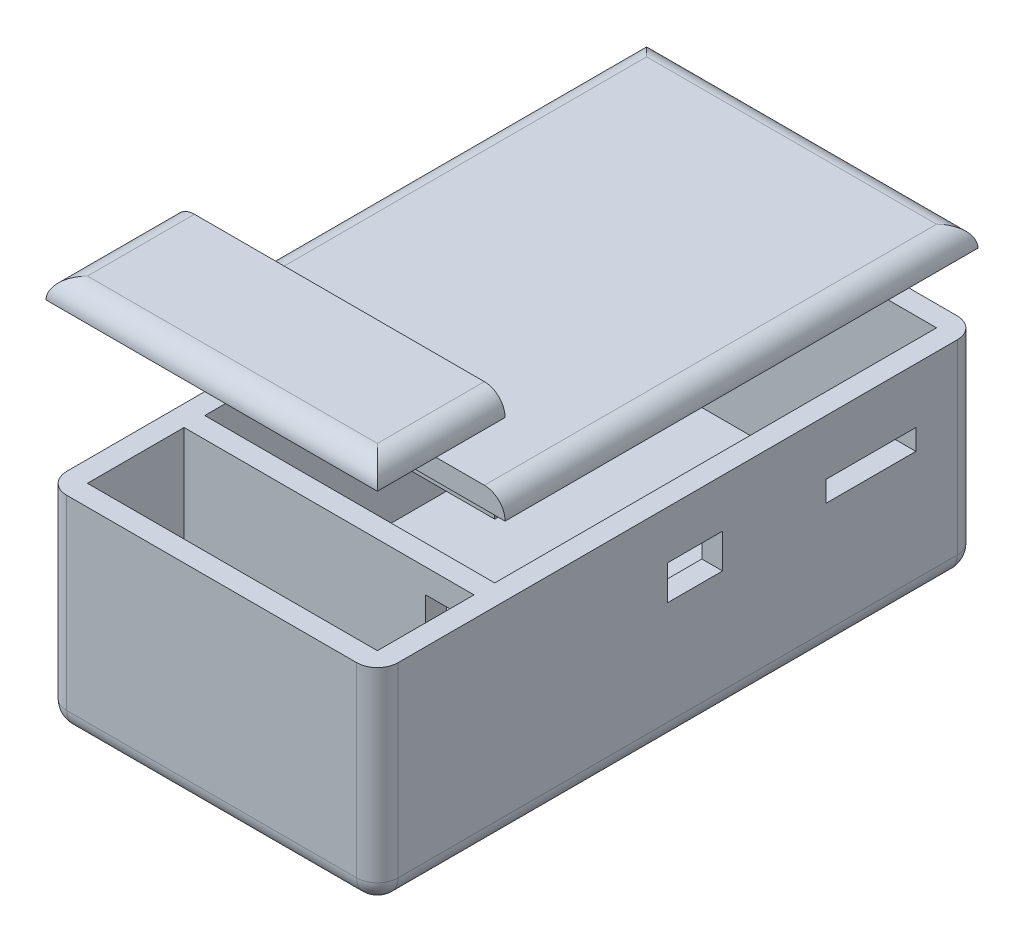
SolidWorks part; units mm, degrees
ref_plane "Front Plane" through (0, 0, 0) normal (0, 0, 1) x (1, 0, 0)
ref_plane "Top Plane" through (0, 0, 0) normal (0, 1, 0) x (1, 0, 0)
ref_plane "Right Plane" through (0, 0, 0) normal (1, 0, 0) x (0, 0, -1)
sketch "Sketch1" plane through (0, 0, 0) normal (0, 1, 0) x (1, 0, 0)
  line L0 (53.34, 40.64) -> (53.34, -12.7) construction
  line L5 (0, 0) -> (53.34, 0)
  line L6 (0, 0) -> (0, 81.28)
  line L11 (0, 81.28) -> (53.34, 81.28)
  line L12 (53.34, 0) -> (53.34, 81.28)
  line L13 (0, -3.81) -> (53.34, -3.81)
  line L14 (0, -3.81) -> (0, -21.59)
  line L15 (0, -21.59) -> (53.34, -21.59)
  line L16 (53.34, -3.81) -> (53.34, -21.59)
  line L17 (0, 40.64) -> (0, -12.7) construction
  dimension "D1" = 3.81
  dimension "D2" = 17.78
  dimension "D3" = 81.28
  dimension "D4" = 53.34
sketch "Sketch3" plane through (0, 0, 0) normal (0, 1, 0) x (1, 0, 0)
  line L0 (53.34, 0) -> (53.34, 81.28) construction
  line L1 (-3.81, -25.4) -> (57.15, -25.4)
  line L2 (-3.81, -25.4) -> (-3.81, 85.09)
  line L3 (-3.81, 85.09) -> (57.15, 85.09)
  line L4 (57.15, -25.4) -> (57.15, 85.09)
  line L5 (0, 81.28) -> (53.34, 81.28) construction
  line L6 (0, 0) -> (0, 81.28) construction
  line L7 (0, -21.59) -> (53.34, -21.59) construction
  dimension "D1" = 3.81
  dimension "D2" = 3.81
  dimension "D3" = 3.81
  dimension "D4" = 3.81
extrude "Boss-Extrude2" add sketch "Sketch3" against normal blind 38.1
extrude "Cut-Extrude1" cut sketch "Sketch1" against normal blind 34.29
sketch "Sketch4" plane through (0, 0, 3.81) normal (0, 0, 1) x (1, 0, 0)
  line L0 (57.15, -38.1) -> (57.15, 0) construction
  line L1 (44.45, -4.445) -> (53.34, -4.445)
  line L2 (44.45, -4.445) -> (44.45, -29.845)
  line L3 (44.45, -29.845) -> (53.34, -29.845)
  line L4 (53.34, -4.445) -> (53.34, -29.845)
  line L5 (57.15, -34.29) -> (-3.81, -34.29) construction
  line L6 (-3.81, -38.1) -> (-3.81, 0) construction
  line L7 (-3.81, -38.1) -> (57.15, -38.1) construction
  line L8 (57.15, -34.29) -> (57.15, 0) construction
  line L9 (53.34, -17.145) -> (57.15, -17.145) construction
  dimension "D1" = 8.89
  dimension "D2" = 25.4
  dimension "D3" = 3.81
  dimension "D4" = 3.81
extrude "Cut-Extrude2" cut sketch "Sketch4" against normal up to surface (3.81 mm away) up to face at (26.67, -17.145, 0)
sketch "Sketch5" plane through (53.34, 0, 0) normal (-1, 0, 0) x (0, 0, 1)
  line L1 (-38.1, -8.89) -> (-27.94, -8.89)
  line L2 (-38.1, -8.89) -> (-38.1, -15.24)
  line L3 (-38.1, -15.24) -> (-27.94, -15.24)
  line L4 (-27.94, -8.89) -> (-27.94, -15.24)
  line L5 (0, -34.29) -> (0, -29.845) construction
  line L6 (0, -34.29) -> (-81.28, -34.29) construction
  line L8 (-81.28, -34.29) -> (-81.28, 0) construction
  line L9 (-73.66, -10.16) -> (-57.15, -10.16)
  line L10 (-73.66, -10.16) -> (-73.66, -13.97)
  line L11 (-73.66, -13.97) -> (-57.15, -13.97)
  line L12 (-57.15, -10.16) -> (-57.15, -13.97)
  line L13 (-57.15, -12.065) -> (-38.1, -12.065) construction
  dimension "D1" = 10.16
  dimension "D2" = 6.35
  dimension "D3" = 38.1
  dimension "D4" = 25.4
  dimension "D5" = 16.51
  dimension "D6" = 3.81
  dimension "D7" = 7.62
extrude "Cut-Extrude3" cut sketch "Sketch5" against normal up to surface (3.81 mm away) up to face at (57.15, -19.05, -29.845)
sketch "Sketch6" plane through (0, 0, 0) normal (1, 0, 0) x (0, 0, -1)
  line L0 (81.28, -34.29) -> (81.28, 0) construction
  line L1 (56.388, -11.049) -> (68.58, -11.049)
  line L2 (56.388, -11.049) -> (56.388, -23.241)
  line L3 (56.388, -23.241) -> (68.58, -23.241)
  line L4 (68.58, -11.049) -> (68.58, -23.241)
  line L5 (68.58, -17.145) -> (81.28, -17.145) construction
  dimension "D1" = 12.192
  dimension "D2" = 12.192
  dimension "D3" = 12.7
extrude "Cut-Extrude4" cut sketch "Sketch6" against normal up to surface (3.81 mm away) up to face at (-3.81, -19.05, -29.845)
ref_plane "Plane1" through (0, 12.7, 0) normal (0, 1, 0) x (1, 0, 0)
sketch "Sketch8" plane through (0, 12.7, 0) normal (0, 1, 0) x (1, 0, 0)
  line L0 (57.15, -25.4) -> (57.15, 85.09) construction
  line L5 (-3.81, 85.09) -> (57.15, 85.09)
  line L6 (-3.81, 85.09) -> (-3.81, -1.905)
  line L7 (-3.81, -1.905) -> (57.15, -1.905)
  line L8 (57.15, 85.09) -> (57.15, -1.905)
  line L9 (0, 0) -> (53.34, 0) construction
  dimension "D1" = 1.905
extrude "Boss-Extrude3" add sketch "Sketch8" along normal blind 3.81 separate body
ref_plane "Plane2" through (0, 29.21, 0) normal (0, 1, 0) x (1, 0, 0)
sketch "Sketch9" plane through (0, 29.21, 0) normal (0, 1, 0) x (1, 0, 0)
  line L1 (-3.81, -25.4) -> (57.15, -25.4)
  line L2 (-3.81, -25.4) -> (-3.81, -1.905)
  line L3 (-3.81, -1.905) -> (57.15, -1.905)
  line L4 (57.15, -25.4) -> (57.15, -1.905)
extrude "Boss-Extrude4" add sketch "Sketch9" along normal blind 3.81
sketch "Sketch10" plane through (0, 12.7, 0) normal (0, -1, 0) x (1, 0, 0)
  line L0 (57.15, 25.4) -> (57.15, -85.09) construction
  line L1 (0, 0) -> (53.34, 0)
  line L2 (0, 0) -> (0, -81.28)
  line L3 (0, -81.28) -> (53.34, -81.28)
  line L4 (53.34, 0) -> (53.34, -81.28)
  line L5 (57.15, -85.09) -> (-3.81, -85.09) construction
  line L6 (-3.81, -85.09) -> (-3.81, 25.4) construction
  line L14 (53.34, 3.81) -> (0, 3.81) construction
  dimension "D1" = 3.81
  dimension "D2" = 3.81
  dimension "D3" = 3.81
  dimension "D8" = 3.81
extrude "Boss-Extrude5" add sketch "Sketch10" along normal blind 2.54
sketch "Sketch11" plane through (0, 29.21, 0) normal (0, -1, 0) x (1, 0, 0)
  line L0 (-3.81, 25.4) -> (57.15, 25.4) construction
  line L1 (0, 21.59) -> (53.34, 21.59)
  line L2 (0, 21.59) -> (0, 3.81)
  line L3 (0, 3.81) -> (53.34, 3.81)
  line L4 (53.34, 21.59) -> (53.34, 3.81)
  line L5 (57.15, 25.4) -> (57.15, -85.09) construction
  line L6 (-3.81, -85.09) -> (-3.81, 25.4) construction
  line L7 (0, 0) -> (53.34, 0) construction
  dimension "D1" = 3.81
  dimension "D2" = 3.81
  dimension "D3" = 3.81
  dimension "D4" = 3.81
extrude "Boss-Extrude6" add sketch "Sketch11" along normal blind 2.54
fillet "Fillet1" radius 3.81 8 edges at (-3.81, -19.05, 25.4) (57.15, -19.05, 25.4) (-3.81, -19.05, -85.09) (57.15, -19.05, -85.09) (26.67, -38.1, -85.09) (-3.81, -38.1, -29.845) (26.67, -38.1, 25.4) (57.15, -38.1, -29.845)
fillet "Fillet2" radius 3.81 3 edges at (57.15, 16.51, -41.5925) (26.67, 16.51, -85.09) (-3.81, 16.51, -41.5925)
fillet "Fillet3" radius 3.81 3 edges at (57.15, 33.02, 13.6525) (26.67, 33.02, 25.4) (-3.81, 33.02, 13.6525)
sketch "Sketch12" plane through (0, 10.16, 0) normal (0, -1, 0) x (1, 0, 0)
  line L0 (0, 0) -> (0, -81.28) construction
  line L1 (5.08, -5.08) -> (48.26, -5.08)
  line L2 (5.08, -5.08) -> (5.08, -76.2)
  line L3 (5.08, -76.2) -> (48.26, -76.2)
  line L4 (48.26, -5.08) -> (48.26, -76.2)
  line L5 (53.34, -81.28) -> (53.34, 0) construction
  line L6 (53.34, 0) -> (0, 0) construction
  line L7 (0, -81.28) -> (53.34, -81.28) construction
  dimension "D1" = 5.08
  dimension "D2" = 5.08
  dimension "D3" = 5.08
  dimension "D4" = 5.08
extrude "Cut-Extrude5" cut sketch "Sketch12" against normal blind 2.54
